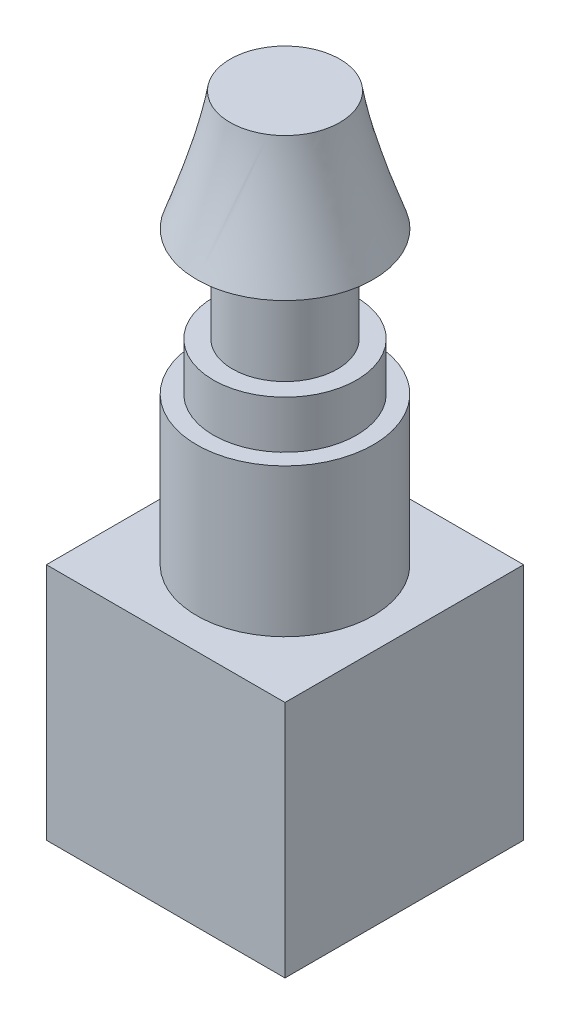
SolidWorks part; units mm, degrees
ref_plane "Front Plane" through (0, 0, 0) normal (0, 0, 1) x (1, 0, 0)
ref_plane "Top Plane" through (0, 0, 0) normal (0, 1, 0) x (1, 0, 0)
ref_plane "Right Plane" through (0, 0, 0) normal (1, 0, 0) x (0, 0, -1)
sketch "Sketch1" plane through (0, 0, 0) normal (0, 1, 0) x (1, 0, 0)
  circle A0 centre (0, 0) radius 1.85
  dimension "D1" = 3.7
extrude "Boss-Extrude1" add sketch "Sketch1" along normal blind 3.1
sketch "Sketch2" plane through (0, 3.1, 0) normal (0, 1, 0) x (1, 0, 0)
  circle A0 centre (0, 0) radius 1.5
  dimension "D1" = 3
extrude "Boss-Extrude2" add sketch "Sketch2" along normal blind 1
sketch "Sketch3" plane through (0, 4.1, 0) normal (0, 1, 0) x (1, 0, 0)
  circle A0 centre (0, 0) radius 1.1
  dimension "D1" = 2.2
extrude "Boss-Extrude3" add sketch "Sketch3" along normal blind 2
sketch "Sketch4" plane through (0, 6.1, 0) normal (0, 1, 0) x (1, 0, 0)
  circle A0 centre (0, 0) radius 1.85
  dimension "D1" = 3.7
ref_plane "Plane1" through (0, 8.6, 0) normal (0, 1, 0) x (1, 0, 0)
sketch "Sketch5" plane through (0, 8.6, 0) normal (0, 1, 0) x (1, 0, 0)
  circle A0 centre (0, 0) radius 1.15
  dimension "D1" = 2.3
loft "Loft1" add profiles "Sketch4", "Sketch5" connector at (0, 6.1, 1.85) connector at (0.6205, 8.6, 0.9683)
sketch "Sketch6" plane through (0, 0, 0) normal (0, -1, 0) x (1, 0, 0)
  line L1 (-2.5, 2.5) -> (2.5, 2.5)
  line L2 (-2.5, 2.5) -> (-2.5, -2.5)
  line L3 (-2.5, -2.5) -> (2.5, -2.5)
  line L4 (2.5, 2.5) -> (2.5, -2.5)
  line L5 (-2.5, 2.5) -> (2.5, -2.5) construction
  line L6 (-2.5, -2.5) -> (2.5, 2.5) construction
  point P0 (0, 0)
  dimension "D1" = 5
  dimension "D2" = 5
extrude "Boss-Extrude4" add sketch "Sketch6" along normal blind 5
sketch "Sketch7" plane through (0, -5, 0) normal (0, -1, 0) x (1, 0, 0)
  circle A0 centre (0, 0) radius 0.9
  dimension "D1" = 1.8
extrude "Cut-Extrude1" cut sketch "Sketch7" against normal blind 3
